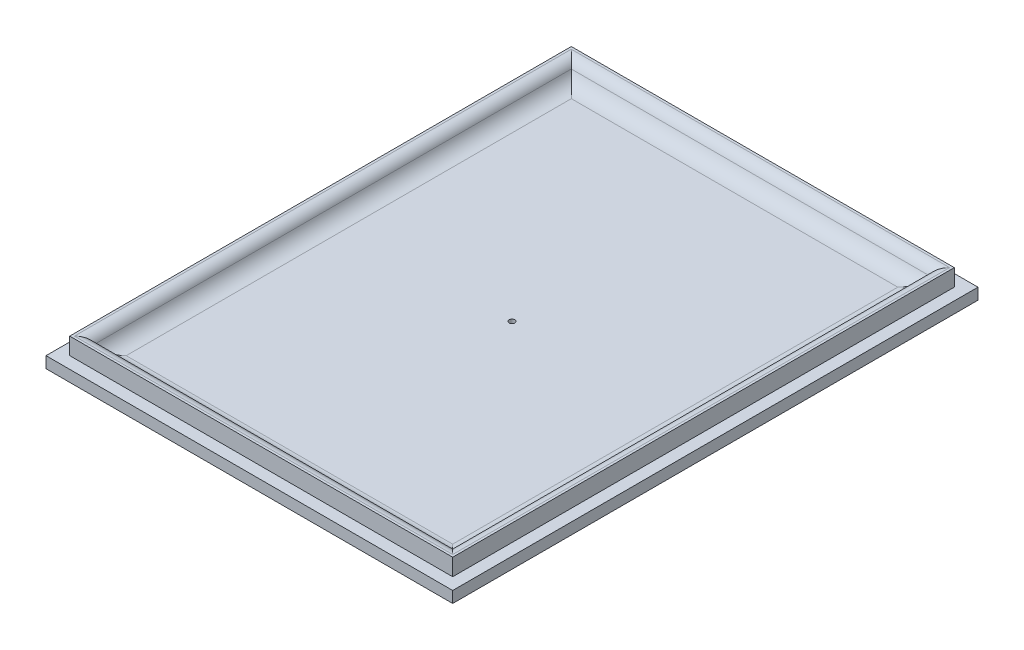
SolidWorks part; units mm, degrees
ref_plane "Front" through (0, 0, 0) normal (0, 0, 1) x (1, 0, 0)
ref_plane "Top" through (0, 0, 0) normal (0, 1, 0) x (1, 0, 0)
ref_plane "Right" through (0, 0, 0) normal (1, 0, 0) x (0, 0, -1)
sketch "Sketch1" plane through (0, 0, 0) normal (0, 1, 0) x (1, 0, 0)
  line L1 (0, 0) -> (144, 0)
  line L2 (0, 0) -> (0, -186)
  line L3 (0, -186) -> (144, -186)
  line L4 (144, 0) -> (144, -186)
  dimension "D1" = 144
  dimension "D2" = 186
extrude "Boss-Extrude1" add sketch "Sketch1" along normal blind 4
sketch "Sketch2" plane through (0, 4, 0) normal (0, 1, 0) x (1, 0, 0)
  line L0 (4.2, -4.2) -> (4.2, -181.8)
  line L1 (0, 0) -> (144, 0)
  line L2 (0, 0) -> (0, -186)
  line L3 (0, -186) -> (144, -186)
  line L4 (144, 0) -> (144, -186)
  line L5 (4.2, -181.8) -> (139.8, -181.8)
  line L6 (139.8, -4.2) -> (139.8, -181.8)
  line L7 (4.2, -4.2) -> (139.8, -4.2)
  line L8 (8.2, -8.2) -> (8.2, -177.8)
  line L9 (8.2, -177.8) -> (135.8, -177.8)
  line L10 (135.8, -8.2) -> (135.8, -177.8)
  line L11 (8.2, -8.2) -> (135.8, -8.2)
  dimension "D1" = 4.2
  dimension "D2" = 4
extrude "Boss-Extrude2" add sketch "Sketch2" along normal blind 6 contours L7 L0 L5 L6 L8 L11 L10 L9 region at (72, 4, 6.4345)
fillet "Fillet1" radius 6 4 edges at (72, 4, 177.8) (135.8, 4, 93) (72, 4, 8.2) (8.2, 4, 93)
fillet "Fillet2" radius 4 4 edges at (72, 10, 8.2) (135.8, 10, 93) (72, 10, 177.8) (8.2, 10, 93)
sketch "Sketch3" plane through (0, 0, 0) normal (0, -1, 0) x (-1, 0, 0)
  circle A0 centre (-72, -93) radius 1
  dimension "D1" = 2
extrude "Cut-Extrude1" cut sketch "Sketch3" against normal blind 6
equation "\"D1@Sketch1\"=144"
equation "\"D2@Sketch1\"=186"
